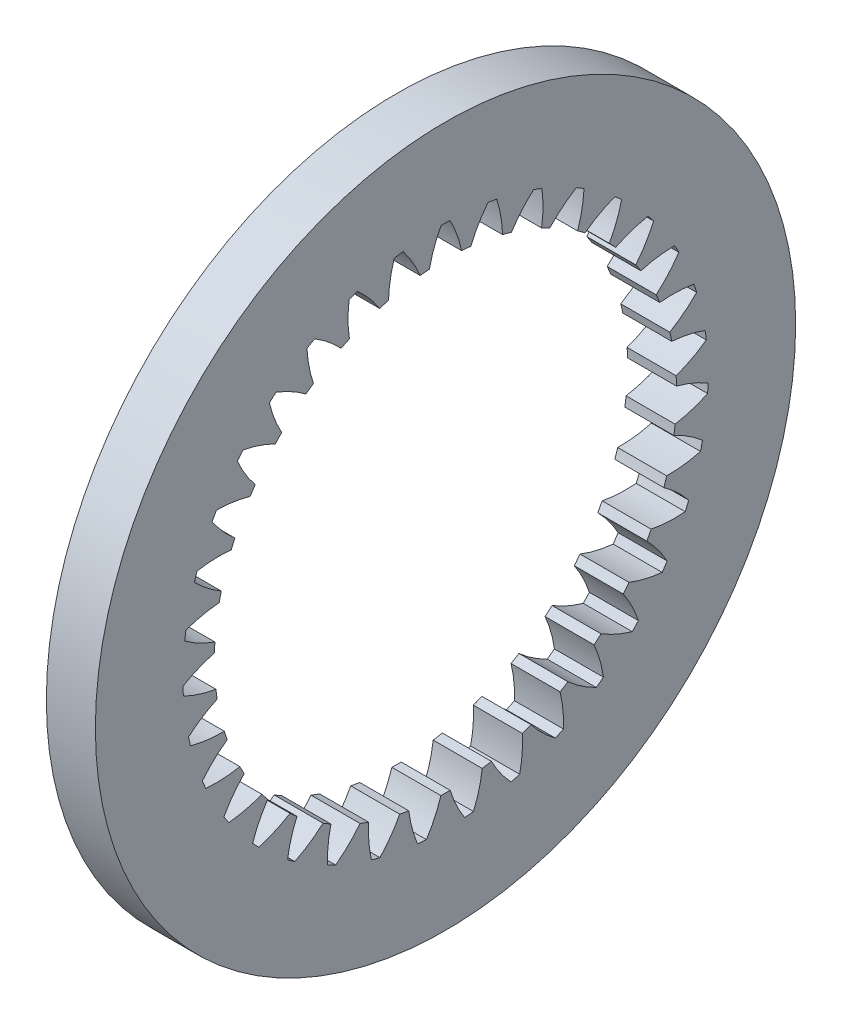
SolidWorks part; units mm, degrees
ref_plane "Front Plane" through (0, 0, 0) normal (0, 0, 1) x (1, 0, 0)
ref_plane "Top Plane" through (0, 0, 0) normal (0, 1, 0) x (1, 0, 0)
ref_plane "Right Plane" through (0, 0, 0) normal (1, 0, 0) x (0, 0, -1)
ref_plane "Plane1" through (-42.5819, 0, 0) normal (1, 0, 0) x (0, 0, -1)
sketch "Sketch1" plane through (-42.5819, 0, 0) normal (1, 0, 0) x (0, 0, -1)
  circle A0 centre (-27.7771, -7.0351) radius 50
  arc A1 (-24.1627, 25.7664) -> (-21.7087, 29.9717) centre (-7.9679, 19.1347) cw
  arc A2 (-21.7087, 29.9717) -> (-20.4553, 29.7442) centre (-27.7771, -7.0351) cw
  arc A3 (-20.4553, 29.7442) -> (-19.6354, 24.9448) centre (-37.1277, 24.4264) cw
  arc A4 (-19.6354, 24.9448) -> (-18.3638, 24.5939) centre (-27.7771, -7.0351) cw
  arc A5 (-18.3638, 24.5939) -> (-15.1984, 28.2934) centre (-3.6135, 15.1771) cw
  arc A6 (-15.1984, 28.2934) -> (-14.0057, 27.8458) centre (-27.7771, -7.0351) cw
  arc A7 (-14.0057, 27.8458) -> (-14.056, 22.9771) centre (-31.3598, 25.5905) cw
  arc A8 (-14.056, 22.9771) -> (-12.8675, 22.4048) centre (-27.7771, -7.0351) cw
  arc A9 (-12.8675, 22.4048) -> (-9.0924, 25.4797) centre (-0.0357, 10.5055) cw
  arc A10 (-9.0924, 25.4797) -> (-7.9988, 24.8263) centre (-27.7771, -7.0351) cw
  arc A11 (-7.9988, 24.8263) -> (-8.9176, 20.0448) centre (-25.4767, 25.7059) cw
  arc A12 (-8.9176, 20.0448) -> (-7.8505, 19.2695) centre (-27.7771, -7.0351) cw
  arc A13 (-7.8505, 19.2695) -> (-3.587, 21.6209) centre (2.6505, 5.2702) cw
  arc A14 (-3.587, 21.6209) -> (-2.6276, 20.7827) centre (-27.7771, -7.0351) cw
  arc A15 (-2.6276, 20.7827) -> (-4.3854, 16.2422) centre (-19.6676, 24.769) cw
  arc A16 (-4.3854, 16.2422) -> (-3.4738, 15.2887) centre (-27.7771, -7.0351) cw
  arc A17 (-3.4738, 15.2887) -> (1.141, 16.8411) centre (4.3587, -0.3606) cw
  arc A18 (1.141, 16.8411) -> (1.9353, 15.8451) centre (-27.7771, -7.0351) cw
  arc A19 (1.9353, 15.8451) -> (-0.605, 11.6914) centre (-14.1191, 22.8098) cw
  arc A20 (-0.605, 11.6914) -> (0.1217, 10.5905) centre (-27.7771, -7.0351) cw
  arc A21 (0.1217, 10.5905) -> (4.9395, 11.2938) centre (5.0341, -6.2059) cw
  arc A22 (4.9395, 11.2938) -> (5.5432, 10.172) centre (-27.7771, -7.0351) cw
  arc A23 (5.5432, 10.172) -> (2.3021, 6.5387) centre (-9.0095, 19.8915) cw
  arc A24 (2.3021, 6.5387) -> (2.8205, 5.3257) centre (-27.7771, -7.0351) cw
  arc A25 (2.8205, 5.3257) -> (7.6865, 5.1575) centre (4.6548, -12.0779) cw
  arc A26 (7.6865, 5.1575) -> (8.0802, 3.9459) centre (-27.7771, -7.0351) cw
  arc A27 (8.0802, 3.9459) -> (4.2423, 0.9497) centre (-4.5032, 16.1077) cw
  arc A28 (4.2423, 0.9497) -> (4.5359, -0.3363) centre (-27.7771, -7.0351) cw
  arc A29 (4.5359, -0.3363) -> (9.2937, -1.3707) centre (3.2332, -17.7878) cw
  arc A30 (9.2937, -1.3707) -> (9.4647, -2.6331) centre (-27.7771, -7.0351) cw
  arc A31 (9.4647, -2.6331) -> (5.1535, -4.8959) centre (-0.7449, 11.5801) cw
  arc A32 (5.1535, -4.8959) -> (5.2127, -6.2137) centre (-27.7771, -7.0351) cw
  arc A33 (5.2127, -6.2137) -> (9.7093, -8.081) centre (0.8149, -23.1521) cw
  arc A34 (9.7093, -8.081) -> (9.6522, -9.3536) centre (-27.7771, -7.0351) cw
  arc A35 (9.6522, -9.3536) -> (5.0063, -10.8103) centre (2.1445, 6.4541) cw
  arc A36 (5.0063, -10.8103) -> (4.8292, -12.1174) centre (-27.7771, -7.0351) cw
  arc A37 (4.8292, -12.1174) -> (8.9202, -14.7576) centre (-2.5224, -27.9984) cw
  arc A38 (8.9202, -14.7576) -> (8.6367, -15.9996) centre (-27.7771, -7.0351) cw
  arc A39 (8.6367, -15.9996) -> (3.8053, -16.6033) centre (4.0722, 0.8947) cw
  arc A40 (3.8053, -16.6033) -> (3.3977, -17.8578) centre (-27.7771, -7.0351) cw
  arc A41 (3.3977, -17.8578) -> (6.9515, -21.1861) centre (-6.6714, -32.1709) cw
  arc A42 (6.9515, -21.1861) -> (6.4508, -22.3575) centre (-27.7771, -7.0351) cw
  arc A43 (6.4508, -22.3575) -> (1.5893, -22.0888) centre (4.9763, -4.9197) cw
  arc A44 (1.5893, -22.0888) -> (0.9642, -23.2504) centre (-27.7771, -7.0351) cw
  arc A45 (0.9642, -23.2504) -> (3.8666, -27.1597) centre (-11.4988, -35.5355) cw
  arc A46 (3.8666, -27.1597) -> (3.1648, -28.2229) centre (-27.7771, -7.0351) cw
  arc A47 (3.1648, -28.2229) -> (-1.5706, -27.0904) centre (4.8277, -10.802) cw
  arc A48 (-1.5706, -27.0904) -> (-2.393, -28.1218) centre (-27.7771, -7.0351) cw
  arc A49 (-2.393, -28.1218) -> (-0.2353, -32.4865) centre (-16.8493, -37.9841) cw
  arc A50 (-0.2353, -32.4865) -> (-1.1156, -33.4072) centre (-27.7771, -7.0351) cw
  arc A51 (-1.1156, -33.4072) -> (-5.5728, -31.4475) centre (3.6311, -16.5633) cw
  arc A52 (-5.5728, -31.4475) -> (-6.5661, -32.3154) centre (-27.7771, -7.0351) cw
  arc A53 (-6.5661, -32.3154) -> (-5.2224, -36.9952) centre (-22.5511, -39.438) cw
  arc A54 (-5.2224, -36.9952) -> (-6.253, -37.744) centre (-27.7771, -7.0351) cw
  arc A55 (-6.253, -37.744) -> (-10.2886, -35.0199) centre (1.425, -22.0183) cw
  arc A56 (-10.2886, -35.0199) -> (-11.421, -35.6965) centre (-27.7771, -7.0351) cw
  arc A57 (-11.421, -35.6965) -> (-10.9345, -40.541) centre (-28.4208, -39.8504) cw
  arc A58 (-10.9345, -40.541) -> (-12.0822, -41.0938) centre (-27.7771, -7.0351) cw
  arc A59 (-12.0822, -41.0938) -> (-15.5665, -37.6929) centre (-1.7197, -26.9918) cw
  arc A60 (-15.5665, -37.6929) -> (-16.8015, -38.1564) centre (-27.7771, -7.0351) cw
  arc A61 (-16.8015, -38.1564) -> (-17.1879, -43.01) centre (-34.2699, -39.2081) cw
  arc A62 (-17.1879, -43.01) -> (-18.4159, -43.3489) centre (-27.7771, -7.0351) cw
  arc A63 (-18.4159, -43.3489) -> (-21.2369, -39.3805) centre (-5.7018, -31.3238) cw
  arc A64 (-21.2369, -39.3805) -> (-22.5348, -39.616) centre (-27.7771, -7.0351) cw
  arc A65 (-22.5348, -39.616) -> (-23.7816, -44.3226) centre (-39.9103, -37.5317) cw
  arc A66 (-23.7816, -44.3226) -> (-25.0504, -44.4368) centre (-27.7771, -7.0351) cw
  arc A67 (-25.0504, -44.4368) -> (-27.1175, -40.0285) centre (-10.3935, -34.8751) cw
  arc A68 (-27.1175, -40.0285) -> (-28.4366, -40.0285) centre (-27.7771, -7.0351) cw
  arc A69 (-28.4366, -40.0285) -> (-30.5038, -44.4368) centre (-45.1607, -34.8751) cw
  arc A70 (-30.5038, -44.4368) -> (-31.7726, -44.3226) centre (-27.7771, -7.0351) cw
  arc A71 (-31.7726, -44.3226) -> (-33.0193, -39.616) centre (-15.6439, -37.5317) cw
  arc A72 (-33.0193, -39.616) -> (-34.3172, -39.3805) centre (-27.7771, -7.0351) cw
  arc A73 (-34.3172, -39.3805) -> (-37.1383, -43.3489) centre (-49.8523, -31.3238) cw
  arc A74 (-37.1383, -43.3489) -> (-38.3663, -43.01) centre (-27.7771, -7.0351) cw
  arc A75 (-38.3663, -43.01) -> (-38.7526, -38.1564) centre (-21.2843, -39.2081) cw
  arc A76 (-38.7526, -38.1564) -> (-39.9876, -37.6929) centre (-27.7771, -7.0351) cw
  arc A77 (-39.9876, -37.6929) -> (-43.4719, -41.0938) centre (-53.8345, -26.9918) cw
  arc A78 (-43.4719, -41.0938) -> (-44.6197, -40.541) centre (-27.7771, -7.0351) cw
  arc A79 (-44.6197, -40.541) -> (-44.1332, -35.6965) centre (-27.1333, -39.8504) cw
  arc A80 (-44.1332, -35.6965) -> (-45.2656, -35.0199) centre (-27.7771, -7.0351) cw
  arc A81 (-45.2656, -35.0199) -> (-49.3011, -37.744) centre (-56.9792, -22.0183) cw
  arc A82 (-49.3011, -37.744) -> (-50.3318, -36.9952) centre (-27.7771, -7.0351) cw
  arc A83 (-50.3318, -36.9952) -> (-48.988, -32.3154) centre (-33.0031, -39.438) cw
  arc A84 (-48.988, -32.3154) -> (-49.9814, -31.4475) centre (-27.7771, -7.0351) cw
  arc A85 (-49.9814, -31.4475) -> (-54.4385, -33.4072) centre (-59.1852, -16.5633) cw
  arc A86 (-54.4385, -33.4072) -> (-55.3189, -32.4865) centre (-27.7771, -7.0351) cw
  arc A87 (-55.3189, -32.4865) -> (-53.1611, -28.1218) centre (-38.7049, -37.9841) cw
  arc A88 (-53.1611, -28.1218) -> (-53.9836, -27.0904) centre (-27.7771, -7.0351) cw
  arc A89 (-53.9836, -27.0904) -> (-58.719, -28.2229) centre (-60.3818, -10.802) cw
  arc A90 (-58.719, -28.2229) -> (-59.4208, -27.1597) centre (-27.7771, -7.0351) cw
  arc A91 (-59.4208, -27.1597) -> (-56.5184, -23.2504) centre (-44.0554, -35.5355) cw
  arc A92 (-56.5184, -23.2504) -> (-57.1435, -22.0888) centre (-27.7771, -7.0351) cw
  arc A93 (-57.1435, -22.0888) -> (-62.005, -22.3575) centre (-60.5305, -4.9197) cw
  arc A94 (-62.005, -22.3575) -> (-62.5057, -21.1861) centre (-27.7771, -7.0351) cw
  arc A95 (-62.5057, -21.1861) -> (-58.9519, -17.8578) centre (-48.8828, -32.1709) cw
  arc A96 (-58.9519, -17.8578) -> (-59.3595, -16.6033) centre (-27.7771, -7.0351) cw
  arc A97 (-59.3595, -16.6033) -> (-64.1908, -15.9996) centre (-59.6264, 0.8947) cw
  arc A98 (-64.1908, -15.9996) -> (-64.4743, -14.7576) centre (-27.7771, -7.0351) cw
  arc A99 (-64.4743, -14.7576) -> (-60.3834, -12.1174) centre (-53.0318, -27.9984) cw
  arc A100 (-60.3834, -12.1174) -> (-60.5604, -10.8103) centre (-27.7771, -7.0351) cw
  arc A101 (-60.5604, -10.8103) -> (-65.2063, -9.3536) centre (-57.6987, 6.4541) cw
  arc A102 (-65.2063, -9.3536) -> (-65.2635, -8.081) centre (-27.7771, -7.0351) cw
  arc A103 (-65.2635, -8.081) -> (-60.7669, -6.2137) centre (-56.3691, -23.1521) cw
  arc A104 (-60.7669, -6.2137) -> (-60.7077, -4.8959) centre (-27.7771, -7.0351) cw
  arc A105 (-60.7077, -4.8959) -> (-65.0188, -2.6331) centre (-54.8092, 11.5801) cw
  arc A106 (-65.0188, -2.6331) -> (-64.8478, -1.3707) centre (-27.7771, -7.0351) cw
  arc A107 (-64.8478, -1.3707) -> (-60.09, -0.3363) centre (-58.7874, -17.7878) cw
  arc A108 (-60.09, -0.3363) -> (-59.7965, 0.9497) centre (-27.7771, -7.0351) cw
  arc A109 (-59.7965, 0.9497) -> (-63.6343, 3.9459) centre (-51.051, 16.1077) cw
  arc A110 (-63.6343, 3.9459) -> (-63.2407, 5.1575) centre (-27.7771, -7.0351) cw
  arc A111 (-63.2407, 5.1575) -> (-58.3747, 5.3257) centre (-60.209, -12.0779) cw
  arc A112 (-58.3747, 5.3257) -> (-57.8562, 6.5387) centre (-27.7771, -7.0351) cw
  arc A113 (-57.8562, 6.5387) -> (-61.0974, 10.172) centre (-46.5446, 19.8915) cw
  arc A114 (-61.0974, 10.172) -> (-60.4937, 11.2938) centre (-27.7771, -7.0351) cw
  arc A115 (-60.4937, 11.2938) -> (-55.6758, 10.5905) centre (-60.5882, -6.2059) cw
  arc A116 (-55.6758, 10.5905) -> (-54.9492, 11.6914) centre (-27.7771, -7.0351) cw
  arc A117 (-54.9492, 11.6914) -> (-57.4895, 15.8451) centre (-41.4351, 22.8098) cw
  arc A118 (-57.4895, 15.8451) -> (-56.6952, 16.8411) centre (-27.7771, -7.0351) cw
  arc A119 (-56.6952, 16.8411) -> (-52.0803, 15.2887) centre (-59.9129, -0.3606) cw
  arc A120 (-52.0803, 15.2887) -> (-51.1688, 16.2422) centre (-27.7771, -7.0351) cw
  arc A121 (-51.1688, 16.2422) -> (-52.9266, 20.7827) centre (-35.8866, 24.769) cw
  arc A122 (-52.9266, 20.7827) -> (-51.9672, 21.6209) centre (-27.7771, -7.0351) cw
  arc A123 (-51.9672, 21.6209) -> (-47.7037, 19.2695) centre (-58.2047, 5.2702) cw
  arc A124 (-47.7037, 19.2695) -> (-46.6365, 20.0448) centre (-27.7771, -7.0351) cw
  arc A125 (-46.6365, 20.0448) -> (-47.5553, 24.8263) centre (-30.0775, 25.7059) cw
  arc A126 (-47.5553, 24.8263) -> (-46.4617, 25.4797) centre (-27.7771, -7.0351) cw
  arc A127 (-46.4617, 25.4797) -> (-42.6866, 22.4048) centre (-55.5185, 10.5055) cw
  arc A128 (-42.6866, 22.4048) -> (-41.4982, 22.9771) centre (-27.7771, -7.0351) cw
  arc A129 (-41.4982, 22.9771) -> (-41.5484, 27.8458) centre (-24.1944, 25.5905) cw
  arc A130 (-41.5484, 27.8458) -> (-40.3557, 28.2934) centre (-27.7771, -7.0351) cw
  arc A131 (-40.3557, 28.2934) -> (-37.1903, 24.5939) centre (-51.9407, 15.1771) cw
  arc A132 (-37.1903, 24.5939) -> (-35.9188, 24.9448) centre (-27.7771, -7.0351) cw
  arc A133 (-35.9188, 24.9448) -> (-35.0989, 29.7442) centre (-18.4264, 24.4264) cw
  arc A134 (-35.0989, 29.7442) -> (-33.8455, 29.9717) centre (-27.7771, -7.0351) cw
  arc A135 (-33.8455, 29.9717) -> (-31.3915, 25.7664) centre (-47.5863, 19.1347) cw
  arc A136 (-31.3915, 25.7664) -> (-30.0777, 25.8847) centre (-27.7771, -7.0351) cw
  arc A137 (-30.0777, 25.8847) -> (-28.414, 30.4605) centre (-12.959, 22.2512) cw
  arc A138 (-28.414, 30.4605) -> (-27.1401, 30.4605) centre (-27.7771, -7.0351) cw
  arc A139 (-27.1401, 30.4605) -> (-25.4765, 25.8847) centre (-42.5951, 22.2512) cw
  arc A140 (-25.4765, 25.8847) -> (-24.1627, 25.7664) centre (-27.7771, -7.0351) cw
extrude "Boss-Extrude1" add sketch "Sketch1" against normal blind 7
